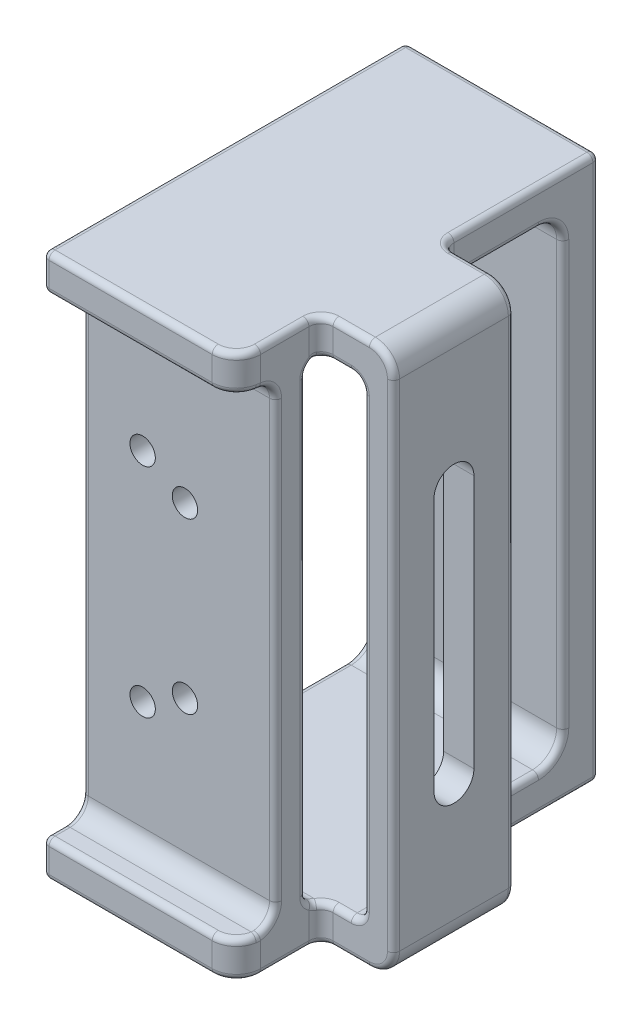
SolidWorks part; units mm, degrees
ref_plane "前视基准面" through (0, 0, 0) normal (0, 0, 1) x (1, 0, 0)
ref_plane "上视基准面" through (0, 0, 0) normal (0, 1, 0) x (1, 0, 0)
ref_plane "右视基准面" through (0, 0, 0) normal (1, 0, 0) x (0, 0, -1)
sketch "草图1" plane through (0, 0, 0) normal (0, 0, 1) x (1, 0, 0)
  line L1 (-8, -22.5) -> (8, -22.5)
  line L2 (-8, -22.5) -> (-8, 22.5)
  line L3 (-8, 22.5) -> (8, 22.5)
  line L4 (8, -22.5) -> (8, 22.5)
  line L5 (-8, -22.5) -> (8, 22.5) construction
  line L6 (-8, 22.5) -> (8, -22.5) construction
  point P0 (0, 0)
  dimension "D1" = 16
  dimension "D2" = 45
extrude "凸台-拉伸1" add sketch "草图1" along normal blind 3
sketch "草图2" plane through (0, 0, 3) normal (0, 0, 1) x (1, 0, 0)
  line L0 (8, -22.5) -> (8, 22.5) construction
  line L1 (-8, 22.5) -> (8, 22.5)
  line L2 (-8, 22.5) -> (-8, 19.5)
  line L3 (-8, 19.5) -> (8, 19.5)
  line L4 (8, 22.5) -> (8, 19.5)
  line L5 (-8, 22.5) -> (-8, -22.5) construction
  line L6 (8, -22.5) -> (-8, -22.5)
  line L7 (8, -22.5) -> (8, -19.5)
  line L8 (8, -19.5) -> (-8, -19.5)
  line L9 (-8, -22.5) -> (-8, -19.5)
  dimension "D1" = 3
  dimension "D2" = 3
extrude "凸台-拉伸2" add sketch "草图2" along normal blind 27
sketch "草图4" plane through (0, 19.5, 0) normal (0, -1, 0) x (1, 0, 0)
  line L0 (-8, 26.7572) -> (8, 26.7572)
  line L1 (8, 30) -> (8, 3) construction
  line L2 (-8, 30) -> (8, 30) construction
  line L3 (-8, 24.2572) -> (8, 24.2572)
  line L4 (-8, 30) -> (-8, 3) construction
  line L5 (-8, 26.7572) -> (-8, 24.2572)
  line L6 (8, 26.7572) -> (8, 24.2572)
  dimension "D1" = 0
  dimension "D2" = 2.5
extrude "凸台-拉伸3" add sketch "草图4" along normal up to next
sketch "草图5" plane through (0, 0, 26.7572) normal (0, 0, 1) x (1, 0, 0)
  line L0 (8, -19.5) -> (8, 19.5) construction
  line L1 (-8, -19.5) -> (-8, 19.5) construction
  circle A0 centre (-3, -9) radius 1.05
  circle A1 centre (-3, 9) radius 1.05
  circle A2 centre (0.5, -7) radius 1.05
  circle A3 centre (0.5, 7) radius 1.05
  point P6 (8, 0)
  dimension "D4" = 2.1
  dimension "D5" = 2.1
  dimension "D9" = 2.1
  dimension "D10" = 2.1
  dimension "D1" = 18
  dimension "D2" = 9
  dimension "D3" = 5
  dimension "D6" = 14
  dimension "D7" = 7
  dimension "D8" = 8.5
extrude "切除-拉伸1" cut sketch "草图5" against normal blind 3
sketch "草图9" plane through (8, 0, 0) normal (1, 0, 0) x (0, 0, -1)
  line L0 (-30, -22.5) -> (0, -22.5) construction
  line L1 (-23, -22.5) -> (-13, -22.5)
  line L2 (-23, -22.5) -> (-23, 22.5)
  line L3 (-23, 22.5) -> (-13, 22.5)
  line L4 (-13, -22.5) -> (-13, 22.5)
  line L5 (-30, 22.5) -> (0, 22.5) construction
  line L6 (0, -22.5) -> (0, 22.5) construction
  line L7 (-24.2572, -19.5) -> (-3, -19.5) construction
  line L8 (-23, -22.5) -> (-13, -22.5)
  line L9 (-23, -22.5) -> (-23, -19.5)
  line L10 (-23, -19.5) -> (-13, -19.5)
  line L11 (-13, -22.5) -> (-13, -19.5)
  line L12 (-24.2572, 19.5) -> (-3, 19.5) construction
  line L13 (-13, 22.5) -> (-23, 22.5)
  line L14 (-13, 22.5) -> (-13, 19.5)
  line L15 (-13, 19.5) -> (-23, 19.5)
  line L16 (-23, 22.5) -> (-23, 19.5)
  line M8 (-30, -22.5) -> (0, -22.5)
  line M10 (0, 22.5) -> (-30, 22.5)
  line M13 (-24.2572, 19.5) -> (-3, 19.5)
  line M15 (-3, -19.5) -> (-24.2572, -19.5)
  dimension "D1" = 10
  dimension "D2" = 13
extrude "凸台-拉伸4" add sketch "草图9" along normal blind 6 contours L4 L2 M8 M15 | L4 L2 M13 M10 region at (8, -21, 18) region at (8, 21, 18)
sketch "草图11" plane through (14, 0, 0) normal (1, 0, 0) x (0, 0, -1)
  line L1 (-23, 22.5) -> (-13, 22.5)
  line L2 (-23, 22.5) -> (-23, -22.5)
  line L3 (-23, -22.5) -> (-13, -22.5)
  line L4 (-13, 22.5) -> (-13, -22.5)
  line L5 (-19.65, -10.5) -> (-16.35, -10.5)
  line L6 (-19.65, -10.5) -> (-19.65, 10.5)
  line L7 (-19.65, 10.5) -> (-16.35, 10.5)
  line L8 (-16.35, -10.5) -> (-16.35, 10.5)
  line L9 (-19.65, -10.5) -> (-16.35, 10.5) construction
  line L10 (-19.65, 10.5) -> (-16.35, -10.5) construction
  circle A0 centre (-18, -10.5) radius 1.65
  circle A1 centre (-18, 10.5) radius 1.65
  point P6 (-18, 0)
  point P11 (-23, 0)
  point P12 (-18, -22.5)
  line M5 (-13, -19.5) -> (-23, -19.5)
  dimension "D1" = 3.3
  dimension "D2" = 21
extrude "凸台-拉伸5" add sketch "草图11" against normal blind 2.5 contours L4 L1 L2 A1 L8 A0 L6 M5 region at (14, 22.0683, 18)
fillet "圆角1" radius 2 2 edges at (8, 21, 30) (8, -21, 30)
fillet "圆角4" radius 1.5 2 edges at (0, 19.5, 26.7572) (0, -19.5, 26.7572)
fillet "圆角6" radius 1 4 edges at (8, 21, 13) (8, -21, 13) (8, 21, 23) (8, -21, 23)
fillet "圆角7" radius 2 2 edges at (14, -22.5, 18) (14, 22.5, 18)
fillet "圆角8" radius 1 2 edges at (0, -19.5, 24.2572) (0, 19.5, 24.2572)
fillet "圆角9" radius 2 2 edges at (0, -19.5, 3) (0, 19.5, 3)
fillet "圆角10" radius 1 2 edges at (11.5, -19.5, 18) (11.5, 19.5, 18)
fillet "圆角11" radius 0.5 22 edges at (8, -22.5, 26) (8.2929, -22.5, 12.7071) (10.5, -22.5, 13) (13.4142, -21.9142, 13) (14, 0, 13) (13.4142, 21.9142, 13) (10.5, 22.5, 13) (8.2929, 22.5, 12.7071) (-1, -22.5, 30) (7.4142, -22.5, 29.4142) (8.2929, -22.5, 23.2929) (10.5, -22.5, 23) (13.4142, -21.9142, 23) (14, 0, 23) (13.4142, 21.9142, 23) (10.5, 22.5, 23) (8.2929, 22.5, 23.2929) (8, 22.5, 26) (7.4142, 22.5, 29.4142) (0, 22.5, 0) (-1, 22.5, 30) (-8, 22.5, 15)
fillet "圆角13" radius 0.5 22 edges at (-7.8536, 22.3536, 29.8536) (-7.8536, 22.3536, 0.1464) (7.8536, 22.3536, 0.1464) (-8, 20.75, 30) (-8, 0, 26.7572) (-8, -20.75, 30) (-8, -22.3536, 29.8536) (-8, 18.9142, 3.5858) (-8, 0, 3) (-8, -18.9142, 3.5858) (-8, -19.5, 29.1286) (-8, -19.2071, 23.9643) (-8, 0, 24.2572) (-8, 19.2071, 23.9643) (-8, 19.5, 29.1286) (-8, -0.25, 0) (7.8536, -22.3536, 0) (8, 0, 0) (-8, -22.5, 14.75) (-0.25, -22.5, 0) (-8, 19.0607, 27.1965) (-8, -19.0607, 27.1965)
fillet "圆角14" radius 0.5 35 edges at (-0.75, 19.5, 30) (7.3202, 19.5, 29.5024) (-0.75, -19.5, 30) (7.3202, -19.5, 29.5024) (8.0467, -19.3975, 23.6981) (8.6414, -19.5, 23.0665) (9.75, -19.5, 23) (11.2071, -19.2071, 23) (11.5, 0, 23) (11.2071, 19.2071, 23) (9.75, 19.5, 23) (8.6414, 19.5, 23.0665) (8.1025, 19.4533, 23.5591) (8.2929, 19.5, 12.7071) (9.75, 19.5, 13) (11.2071, 19.2071, 13) (11.5, 0, 13) (11.2071, -19.2071, 13) (9.75, -19.5, 13) (8.2929, -19.5, 12.7071) (8, -18.9655, 27.1092) (8, 0, 26.7572) (8, 18.9655, 27.1092) (8, 18.8586, 24.1907) (8, 0, 24.2572) (8, -18.8586, 24.1907) (8, -19.5, 8.5) (8, -18.9142, 3.5858) (8, 0, 3) (8, 18.9142, 3.5858) (8, 19.5, 8.5) (-7.8536, 19.6464, 29.8536) (-7.8536, -19.6464, 29.8536)
sketch "草图12" plane through (0, 0, 3) normal (0, 0, 1) x (1, 0, 0)
  line L0 (7.5, 17.5) -> (-7.5, 17.5) construction
  line L1 (-7.5, 17.5) -> (-7.5, -17.5) construction
  circle A0 centre (0, 15) radius 1.6
  circle A1 centre (0, -15) radius 1.6
  point P6 (0, 17.5)
  point P9 (-7.5, 0)
  dimension "D3" = 3.2
  dimension "D4" = 3.2
  dimension "D1" = 30
  dimension "D2" = 15
extrude "切除-拉伸2" cut sketch "草图12" against normal blind 10
